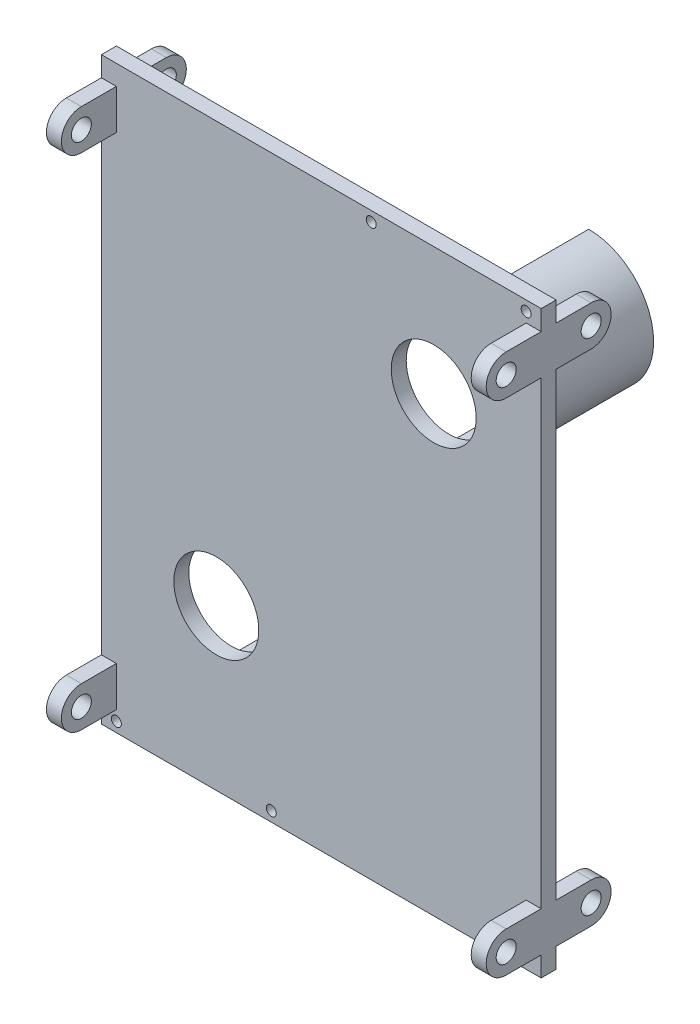
SolidWorks part; units mm, degrees
ref_plane "Front Plane" through (0, 0, 0) normal (0, 0, 1) x (1, 0, 0)
ref_plane "Top Plane" through (0, 0, 0) normal (0, 1, 0) x (1, 0, 0)
ref_plane "Right Plane" through (0, 0, 0) normal (1, 0, 0) x (0, 0, -1)
sketch "Sketch1" plane through (0, 0, 0) normal (0, 0, 1) x (1, 0, 0)
  line L1 (-44, -58) -> (44, -58)
  line L2 (-44, -58) -> (-44, 58)
  line L3 (-44, 58) -> (44, 58)
  line L4 (44, -58) -> (44, 58)
  line L5 (-44, -58) -> (44, 58) construction
  line L6 (-44, 58) -> (44, -58) construction
  circle A0 centre (-22.8181, 25.0296) radius 20 construction
  circle A1 centre (24.0245, 19.8034) radius 20 construction
  point P0 (0, 0)
  dimension "D3" = 40
  dimension "D1" = 88
  dimension "D2" = 116
extrude "Boss-Extrude1" add sketch "Sketch1" along normal blind 3 contours L3 L4 L1 L2
sketch "Sketch2" plane through (0, 0, 3) normal (0, 0, 1) x (1, 0, 0)
  line L0 (-44, -58) -> (-44, 58) construction
  line L1 (-44, 58) -> (44, 58) construction
  line L2 (44, 0) -> (-44, 0) construction
  line L3 (44, -58) -> (44, 58) construction
  line L4 (-44, -58) -> (44, -58) construction
  circle A0 centre (-22.5, 32.5) radius 20 construction
  circle A1 centre (21, -26) radius 20 construction
  circle A2 centre (-22.5, 32.5) radius 8.5
  circle A3 centre (21, -26) radius 8.5
  dimension "D2" = 40
  dimension "D6" = 17
  dimension "D4" = 26
  dimension "D5" = 32.5
  dimension "D3" = 23
  dimension "D1" = 43.5
  dimension "D7" = 25.5
  dimension "D8" = 32
extrude "Cut-Extrude1" cut sketch "Sketch2" against normal through all
sketch "Sketch4" plane through (-44, 0, 0) normal (-1, 0, 0) x (0, 0, 1)
  line L0 (0, 0) -> (10.9251, 0) construction
  line L1 (0, 58) -> (0, 50) construction
  line L2 (0, -58) -> (0, 58) construction
  line L3 (0, 50) -> (-7, 50) construction
  line L4 (-7, 54) -> (0, 54)
  line L5 (0, 54) -> (0, 46)
  line L6 (0, 46) -> (-7, 46)
  line L7 (0, -50) -> (-7, -50) construction
  line L8 (0, -58) -> (0, -50) construction
  line L9 (0, -46) -> (-7, -46)
  line L10 (0, -54) -> (0, -46)
  line L11 (-7, -54) -> (0, -54)
  line L12 (1.5, -58) -> (1.5, -62.9921) construction
  line L13 (3, -58) -> (0, -58) construction
  line L14 (3, 46) -> (10, 46)
  line L15 (3, 54) -> (3, 46)
  line L16 (10, 54) -> (3, 54)
  line L17 (10, -54) -> (3, -54)
  line L18 (3, -54) -> (3, -46)
  line L19 (3, -46) -> (10, -46)
  circle A0 centre (-7, 50) radius 2
  arc A1 (-7, 54) -> (-7, 46) centre (-7, 50) ccw
  arc A2 (-7, -54) -> (-7, -46) centre (-7, -50) cw
  circle A3 centre (-7, -50) radius 2
  circle A4 centre (10, 50) radius 2
  arc A5 (10, 54) -> (10, 46) centre (10, 50) cw
  circle A6 centre (10, -50) radius 2
  arc A7 (10, -54) -> (10, -46) centre (10, -50) ccw
  dimension "D3" = 8
  dimension "D4" = 4
  dimension "D1" = 7
  dimension "D2" = 8
extrude "Boss-Extrude3" add sketch "Sketch4" against normal blind 3
sketch "Sketch6" plane through (0, 0, 3) normal (0, 0, 1) x (1, 0, 0)
  line L0 (-44, 58) -> (-44, 54) construction
  line L1 (-44, 56) -> (-41, 56) construction
  line L2 (-44, 58) -> (-7, 58) construction
  line L3 (44, -58) -> (44, -54) construction
  line L4 (44, -58) -> (44, 58) construction
  line L5 (44, -56) -> (41, -56) construction
  line L6 (41, -56) -> (10, -56) construction
  circle A0 centre (-41, 56) radius 1
  circle A1 centre (-10, 56) radius 1
  circle A2 centre (41, -56) radius 1
  circle A3 centre (10, -56) radius 1
  dimension "D2" = 2
  dimension "D6" = 2
  dimension "D10" = 2
  dimension "D11" = 2
  dimension "D1" = 4
  dimension "D3" = 3
  dimension "D4" = 37
  dimension "D5" = 3
  dimension "D7" = 3
  dimension "D8" = 4
  dimension "D9" = 31
extrude "Cut-Extrude2" cut sketch "Sketch6" against normal blind 10
sketch "Sketch5" plane through (0, 0, 0) normal (0, 0, -1) x (-1, 0, 0)
  line L0 (22.5, 32.5) -> (22.5, 45.5) construction
  line L5 (-21, -26) -> (-21, -13) construction
  line L10 (22.5, 32.5) -> (32.5, 32.5) construction
  line L15 (22.5, 42.5) -> (22.5, 45.5)
  line L16 (22.5, 22.5) -> (22.5, 19.5)
  line L17 (-21, -16) -> (-21, -13)
  line L18 (-21, -36) -> (-21, -39)
  arc A0 (22.5, 22.5) -> (22.5, 42.5) centre (22.5, 32.5) ccw
  arc A1 (22.5, 19.5) -> (22.5, 45.5) centre (22.5, 32.5) ccw
  arc A2 (-21, -36) -> (-21, -16) centre (-21, -26) ccw
  arc A3 (-21, -39) -> (-21, -13) centre (-21, -26) ccw
  point P9 (22.5, 42.5)
  point P20 (-21, -16)
  point P26 (35.5, 32.5)
  dimension "D1" = 20
  dimension "D2" = 3
  dimension "D4" = 3
  dimension "D5" = 20
extrude "Boss-Extrude4" add sketch "Sketch5" along normal blind 28 contours L16 A1 L15 A0 | A3 L17 A2 L18 region at (-22.7907, 44, 0)
mirror "Mirror1" about plane through (0, 0, 0) normal (1, 0, 0) of "Boss-Extrude3"
mirror "Mirror2" about plane through (44, -58, 3) normal (-1, 0, 0) of bodies 107
delete or keep bodies "Body-Delete/Keep 1" type delete bodies bodies 107
equation "\"mini-flipper-shaft-diameter\"= 26mm"
equation "\"mini-shaft-ring-groove-diam\"= 7.8mm"
equation "\"mini-shaft-ring-groove-width\"= 1mm"
equation "\"dtCoverPlate-DistFrom-GearCent\"= 73mm"
equation "\"wormGearShaft-L\"= \"dtCoverPlate-DistFrom-GearCent\" - 27.75 + 3.75"
equation "\"wormGearShaft-Dsmall\"= 6mm"
equation "\"wormGearShaft-Dworm\"= 12mm"
equation "\"wormL-D\" = 12mm"
equation "\"wormR-D\" = 15mm"
equation "\"wormGearL-D\" = 40mm"
equation "\"wormGearR-D\" = 50mm"
equation "\"D5@Sketch2\"=\"wormGearR-D\"/2 + \"wormR-D\"/2"
equation "\"D4@Sketch2\"=\"wormGearL-D\"/2 + \"wormL-D\"/2"
